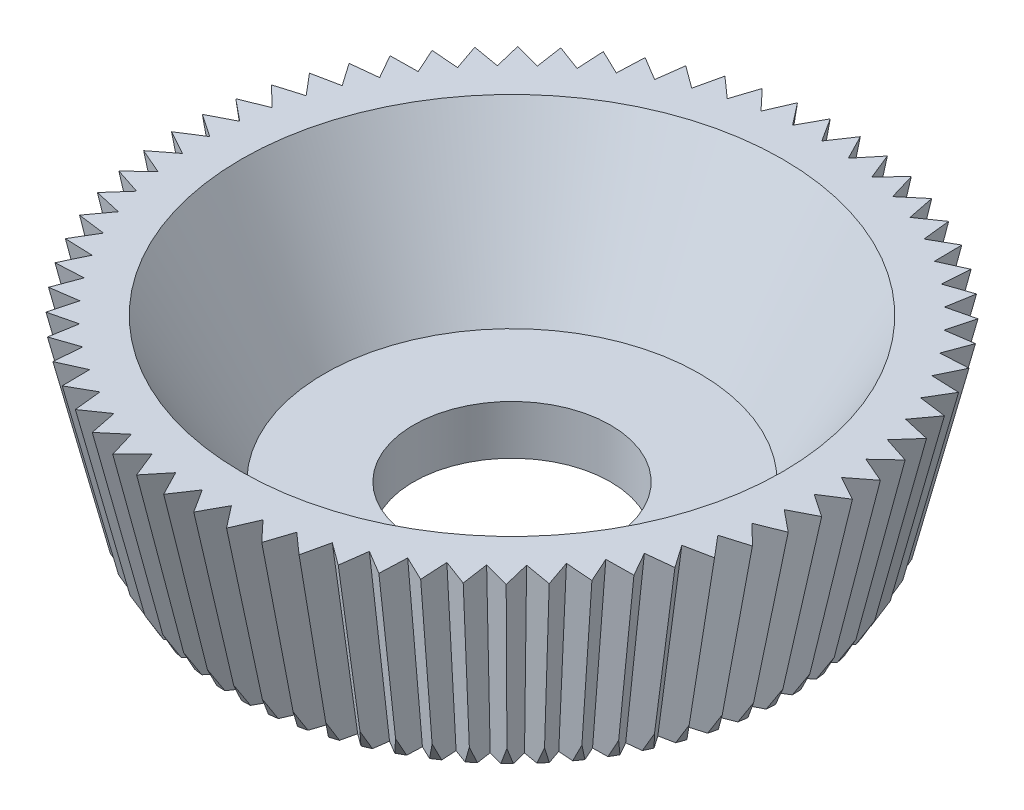
SolidWorks part; units mm, degrees
ref_plane "Front Plane" through (0, 0, 0) normal (0, 0, 1) x (1, 0, 0)
ref_plane "Top Plane" through (0, 0, 0) normal (0, 1, 0) x (1, 0, 0)
ref_plane "Right Plane" through (0, 0, 0) normal (1, 0, 0) x (0, 0, -1)
sketch "Sketch1" plane through (0, 0, 0) normal (0, 0, 1) x (1, 0, 0)
  line L1 (5.5989, 11.0731) -> (7, 13.5)
  line L2 (3.8102, 12.0731) -> (5.5, 15)
  line L4 (0, 11.0731) -> (5.5989, 11.0731) construction
  line L5 (0, 11.0731) -> (0, 15) construction
  line L6 (5.5989, 11.0731) -> (2, 11.0731)
  line L7 (2, 11.0731) -> (2, 12.0731)
  line L8 (2, 12.0731) -> (3.8102, 12.0731)
  line L9 (7, 13.5) -> (7, 15)
  line L10 (7, 15) -> (5.5, 15)
  point P3 (4.867, 9.8055)
  dimension "D1" = 7
  dimension "D2" = 120
  dimension "D3" = 15
  dimension "D4" = 1.5
  dimension "D5" = 1.5
  dimension "D6" = 1
  dimension "D7" = 2
revolve "Revolve1" add sketch "Sketch1" angle 360 about L5
sketch "Sketch2" plane through (0, 15, 0) normal (0, 1, 0) x (1, 0, 0)
  line L0 (0.0575, -6.9998) -> (0.4964, -6.1975)
  line L1 (0.4964, -6.1975) -> (1.0575, -6.9197)
  arc A0 (0.0575, -6.9998) -> (1.0575, -6.9197) centre (0, 0) ccw
  circle A1 centre (0, 0) radius 7 construction
  dimension "D1" = 1
extrude "Cut-Extrude1" cut sketch "Sketch2" against normal through all draft 7 draft outward yes
pattern_circular "CirPattern1" count 68 over 360 about axis through (0, 15, 0) along (0, -1, 0) of "Cut-Extrude1"
sketch "Sketch3" plane through (0, 12.0731, 0) normal (0, 1, 0) x (1, 0, 0)
  line L0 (0, 3.8102) -> (0, 2) construction
  circle A0 centre (0, 2.9051) radius 2
  circle A1 centre (0, 0) radius 3.8102 construction
  circle A2 centre (0, 0) radius 2 construction
  point P10 (0, 2.9051)
  dimension "D1" = 4
